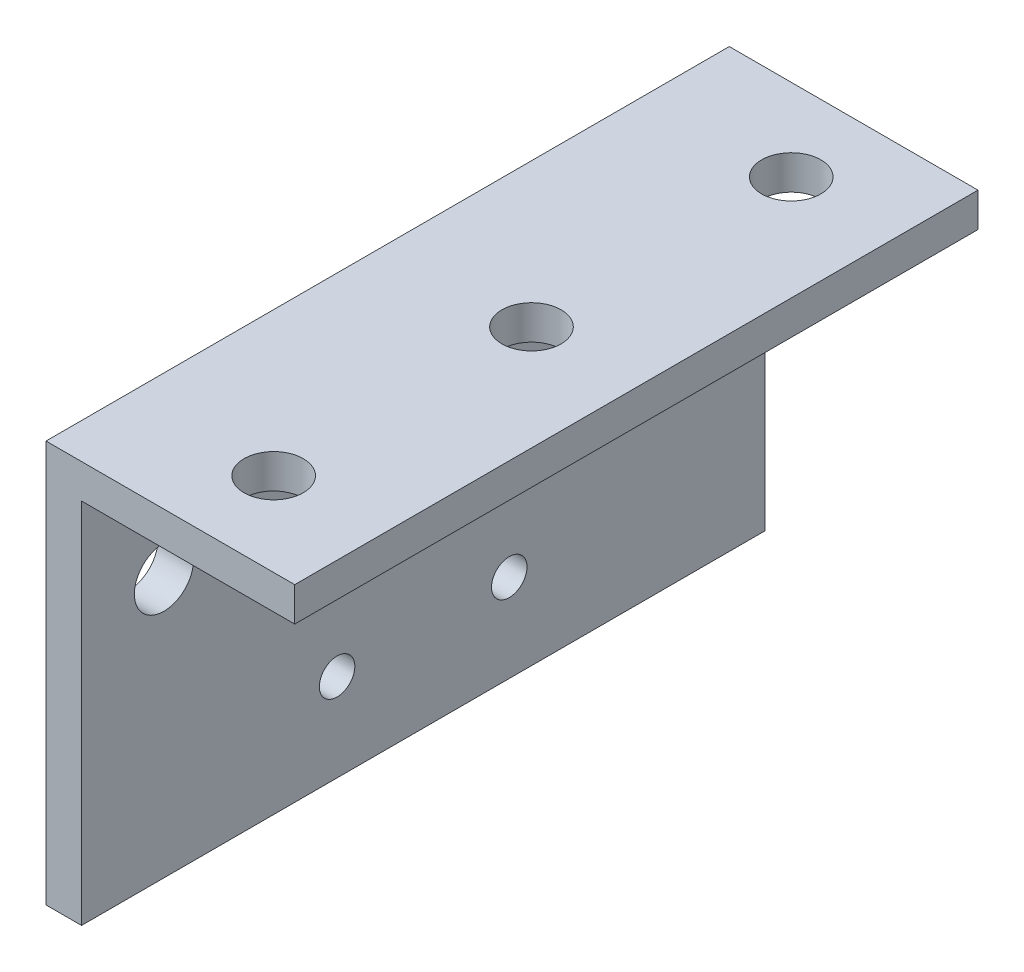
SolidWorks part; units mm, degrees
material "6061 Alloy"
ref_plane "Front Plane" through (0, 0, 0) normal (0, 0, 1) x (1, 0, 0)
ref_plane "Top Plane" through (0, 0, 0) normal (0, 1, 0) x (1, 0, 0)
ref_plane "Right Plane" through (0, 0, 0) normal (1, 0, 0) x (0, 0, -1)
sketch "Sketch1" plane through (0, 0, 0) normal (0, 0, 1) x (1, 0, 0)
  line L0 (0, 0) -> (0, 37.338)
  line L1 (0, 37.338) -> (23.114, 37.338)
  line L2 (23.114, 37.338) -> (23.114, 34.163)
  line L3 (0, 0) -> (3.302, 0)
  line L4 (3.302, 0) -> (3.302, 34.163)
  line L5 (3.302, 34.163) -> (23.114, 34.163)
  dimension "D1" = 37.338
  dimension "D2" = 23.114
  dimension "D3" = 3.175
extrude "Boss-Extrude1" add sketch "Sketch1" along normal blind 63.5
sketch "Sketch21" plane through (0, 0, 0) normal (-1, 0, 0) x (0, 0, 1)
  line L0 (31.75, 0) -> (31.75, 37.338) construction
  line L1 (63.5, 0) -> (0, 0) construction
  line L2 (63.5, 37.338) -> (0, 37.338) construction
  point P3 (31.75, 18.669)
sketch "Sketch28" plane through (0, 37.338, 0) normal (0, 1, 0) x (1, 0, 0)
  line L0 (23.114, -31.75) -> (0, -31.75) construction
  line L2 (23.114, -63.5) -> (23.114, 0) construction
  point P3 (11.557, -31.75)
sketch "Sketch29" plane through (0, 0, 0) normal (-1, 0, 0) x (0, 0, 1)
  line L0 (0, 24.2082) -> (63.5, 24.2082) construction
  line L1 (0, 37.338) -> (0, 0) construction
  line L2 (63.5, 37.338) -> (63.5, 0) construction
sketch "Sketch30" plane through (0, 37.338, 0) normal (0, 1, 0) x (1, 0, 0)
  line L0 (13.3686, 0) -> (13.3686, -63.5) construction
  line L1 (23.114, 0) -> (0, 0) construction
  line L2 (23.114, -63.5) -> (0, -63.5) construction
sketch "Sketch31" plane through (0, 0, 0) normal (-1, 0, 0) x (0, 0, 1)
  line L0 (31.75, 24.2082) -> (10.16, 24.2082) construction
  line L1 (0, 24.2082) -> (63.5, 24.2082) construction
  line L2 (31.75, 24.2082) -> (53.34, 24.2082) construction
sketch "Sketch32" plane through (0, 37.338, 0) normal (0, 1, 0) x (1, 0, 0)
  line L0 (13.3686, -31.75) -> (13.3686, -53.34) construction
  line L1 (13.3686, 0) -> (13.3686, -63.5) construction
  line L2 (13.3686, -31.75) -> (13.3686, -10.16) construction
hole_wizard "M5 Clearance Hole1" positions "Sketch35" profile "Sketch36" hole size "M5" standard "ANSI Metric" end condition through all
sketch "Sketch35" plane through (0, 0, 0) normal (-1, 0, 0) x (0, 0, 1)
  line L0 (0, 24.2082) -> (63.5, 24.2082) construction
  point P0 (55.8413, 24.2082)
sketch "Sketch36" plane through (0, 24.2082, 55.8413) normal (0, 1, 0) x (0, 0, 1)
  line L0 (0, 0) -> (0, 23.114)
  line L1 (0, 23.114) -> (2.75, 23.114)
  line L2 (2.75, 23.114) -> (2.75, 0)
  line L5 (2.75, 0) -> (0, 0)
  line L11 (0, -6.35) -> (0, 107.95) construction
  dimension "Thru Hole Dia." = 5.5
  dimension "Thru Hole Depth" = 23.114
hole_wizard "M5 Clearance Hole2" positions "Sketch37" profile "Sketch38" hole size "M5" standard "ANSI Metric" end condition through all
sketch "Sketch37" plane through (0, 0, 0) normal (-1, 0, 0) x (0, 0, 1)
  line L0 (0, 24.2082) -> (63.5, 24.2082) construction
  point P0 (7.6776, 24.2082)
sketch "Sketch38" plane through (0, 24.2082, 7.6776) normal (0, 1, 0) x (0, 0, 1)
  line L0 (0, 0) -> (0, 23.114)
  line L1 (0, 23.114) -> (2.75, 23.114)
  line L2 (2.75, 23.114) -> (2.75, 0)
  line L5 (2.75, 0) -> (0, 0)
  line L11 (0, -6.35) -> (0, 107.95) construction
  dimension "Thru Hole Dia." = 5.5
  dimension "Thru Hole Depth" = 23.114
hole_wizard "M5 Clearance Hole3" positions "Sketch39" profile "Sketch40" hole size "M5" standard "ANSI Metric" end condition through all
sketch "Sketch39" plane through (0, 37.338, 0) normal (0, 1, 0) x (1, 0, 0)
  point P0 (13.3686, -31.75)
sketch "Sketch40" plane through (13.3686, 37.338, 31.75) normal (1, 0, 0) x (0, 0, 1)
  line L0 (0, 0) -> (0, 37.338)
  line L1 (0, 37.338) -> (2.75, 37.338)
  line L2 (2.75, 37.338) -> (2.75, 0)
  line L5 (2.75, 0) -> (0, 0)
  line L11 (0, -6.35) -> (0, 107.95) construction
  dimension "Thru Hole Dia." = 5.5
  dimension "Thru Hole Depth" = 37.338
hole_wizard "M5 Clearance Hole4" positions "Sketch43" profile "Sketch44" hole size "M5" standard "ANSI Metric" end condition through all
sketch "Sketch43" plane through (0, 37.338, 0) normal (0, 1, 0) x (1, 0, 0)
  line L0 (13.3686, 0) -> (13.3686, -63.5) construction
  point P0 (13.3686, -55.7137)
sketch "Sketch44" plane through (13.3686, 37.338, 55.7137) normal (1, 0, 0) x (0, 0, 1)
  line L0 (0, 0) -> (0, 37.338)
  line L1 (0, 37.338) -> (2.75, 37.338)
  line L2 (2.75, 37.338) -> (2.75, 0)
  line L5 (2.75, 0) -> (0, 0)
  line L11 (0, -6.35) -> (0, 107.95) construction
  dimension "Thru Hole Dia." = 5.5
  dimension "Thru Hole Depth" = 37.338
hole_wizard "M5 Clearance Hole5" positions "Sketch49" profile "Sketch50" hole size "M5" standard "ANSI Metric" end condition through all
sketch "Sketch49" plane through (0, 37.338, 0) normal (0, 1, 0) x (1, 0, 0)
  line L0 (13.3686, 0) -> (13.3686, -63.5) construction
  point P0 (13.3686, -7.6106)
sketch "Sketch50" plane through (13.3686, 37.338, 7.6106) normal (1, 0, 0) x (0, 0, 1)
  line L0 (0, 0) -> (0, 37.338)
  line L1 (0, 37.338) -> (2.75, 37.338)
  line L2 (2.75, 37.338) -> (2.75, 0)
  line L5 (2.75, 0) -> (0, 0)
  line L11 (0, -6.35) -> (0, 107.95) construction
  dimension "Thru Hole Dia." = 5.5
  dimension "Thru Hole Depth" = 37.338
sketch "Sketch51" plane through (0, 0, 0) normal (-1, 0, 0) x (0, 0, 1)
  line L0 (63.5, 34.163) -> (0, 34.163) construction
  line L1 (39.75, 24.163) -> (23.75, 24.163) construction
  line L2 (39.75, 24.163) -> (39.75, 8.163) construction
  line L3 (39.75, 8.163) -> (23.75, 8.163) construction
  line L4 (23.75, 24.163) -> (23.75, 8.163) construction
  line L5 (39.75, 24.163) -> (23.75, 8.163) construction
  line L6 (39.75, 8.163) -> (23.75, 24.163) construction
  line L7 (31.75, 37.338) -> (31.75, 0) construction
  line L8 (63.5, 37.338) -> (0, 37.338) construction
  line L9 (63.5, 0) -> (0, 0) construction
  circle A0 centre (31.75, 16.163) radius 5 construction
  point P0 (31.75, 16.163)
  point P15 (0, 0)
  dimension "D4" = 10
  dimension "D1" = 10
  dimension "D2" = 16
  dimension "D3" = 16
hole_wizard "Tap Drill for M4x0.7 Tap2" positions "Sketch52" profile "Sketch53" hole size "M4x0.7" standard "ANSI Metric" end condition through all
sketch "Sketch52" plane through (0, 0, 0) normal (-1, 0, 0) x (0, 0, 1)
  point P0 (23.75, 24.163)
  point P3 (23.75, 8.163)
  point P6 (39.75, 8.163)
  point P9 (39.75, 24.163)
sketch "Sketch53" plane through (0, 24.163, 23.75) normal (0, 1, 0) x (0, 0, 1)
  line L0 (0, 0) -> (0, 23.114)
  line L1 (0, 23.114) -> (1.65, 23.114)
  line L2 (1.65, 23.114) -> (1.65, 0)
  line L5 (1.65, 0) -> (0, 0)
  line L11 (0, -6.35) -> (0, 107.95) construction
  dimension "Thru Hole Dia." = 3.3
  dimension "Thru Hole Depth" = 23.114
